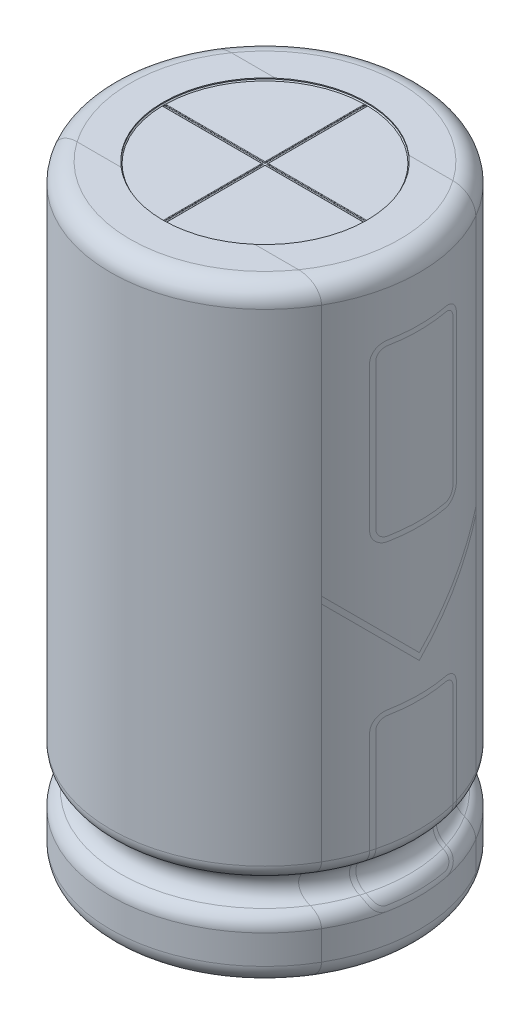
SolidWorks part; units mm, degrees
ref_plane "Front Plane" through (0, 0, 0) normal (0, 0, 1) x (1, 0, 0)
ref_plane "Top Plane" through (0, 0, 0) normal (0, 1, 0) x (1, 0, 0)
ref_plane "Right Plane" through (0, 0, 0) normal (1, 0, 0) x (0, 0, -1)
sketch "Body_Plano" plane through (0, 0, 0) normal (0, 1, 0) x (1, 0, 0)
  circle A0 centre (0, 0) radius 8
  dimension "Diametro" = 16
extrude "Body" add sketch "Body_Plano" along normal blind 31.5
sketch "Cintura_Plano" plane through (0, 0, 0) normal (0, 0, 1) x (1, 0, 0)
  line L0 (8, 31.5) -> (-8, 31.5) construction
  line L1 (0, 0) -> (0, 31.5) construction
  line L2 (-4, 0) -> (-4, 4) construction
  line L3 (-8, 31.5) -> (-8, 0) construction
  line L4 (-6, 4) -> (-7.8125, 4) construction
  line L5 (-4, 4) -> (0, 4) construction
  line L6 (-8, 0) -> (8, 0) construction
  line L7 (-8, 2.5) -> (-8, 5.5)
  line L8 (-6, 3) -> (-7, 3) construction
  line L9 (-4, 2) -> (-8, 2) construction
  line L10 (-6, 2) -> (-6, 4) construction
  line L11 (-7, 3) -> (-7, 2) construction
  line L12 (-7, 2.5) -> (-8, 2.5) construction
  line L13 (-7.5, 2.5) -> (-7.5, 4) construction
  arc A0 (-7.5, 3.25) -> (-7.5, 4.75) centre (-7.8125, 4) ccw
  arc A1 (-7.5, 3.25) -> (-8, 2.5) centre (-7.1875, 2.5) ccw
  arc A2 (-7.5, 4.75) -> (-8, 5.5) centre (-7.1875, 5.5) cw
revolve "Cintura" cut sketch "Cintura_Plano" angle 360 about L1
fillet "F1" radius 1 1 edges at (0, 31.5, 8)
fillet "F2" radius 1 1 edges at (0, 0, 8)
sketch "HS Croquis" plane through (0, 31.5, 0) normal (0, 1, 0) x (1, 0, 0)
  line L0 (0, 0) -> (0, 8) construction
  line L1 (0, 4) -> (6.9282, 4) construction
  circle A0 centre (0, 0) radius 5.2915
  circle A1 centre (0, 0) radius 8 construction
  point P9 (3.4641, 4)
extrude "Hueco Superior" cut sketch "HS Croquis" against normal blind 0.1
sketch "HI Croquis" plane through (0, 0, 0) normal (0, -1, 0) x (1, 0, 0)
  circle A0 centre (0, 0) radius 6.5
  circle A1 centre (0, 0) radius 7 construction
  point P5 (0, 7)
  point P6 (0, 6.5)
  dimension "D1" = 0.5
extrude "Hueco Inferior" cut sketch "HI Croquis" against normal blind 0.1
chamfer "Chaflan Huecos" distance 0.05 angle 45 2 edges at (0, 0.1, -6.5) (0, 31.4, 5.2915)
ref_plane "Plane1" through (8, 0, 0) normal (1, 0, 0) x (0, 0, -1)
sketch "Croquis2" plane through (0, 0.1, 0) normal (0, -1, 0) x (-1, 0, 0)
  line L0 (0, -1.1307) -> (0, 0.9067) construction
  circle A0 centre (-3.75, 0) radius 0.4
  circle A1 centre (3.75, 0) radius 0.4
  dimension "Diametro" = 0.8
  dimension "Pitch" = 7.5
sketch "Croquis3" plane through (0, 31.4, 0) normal (0, 1, 0) x (1, 0, 0)
  line L1 (0, 0.6856) -> (0, -0.5793) construction
  line L2 (-0.0625, 5.2411) -> (-0.0625, 0.0625)
  line L3 (0.829, 0) -> (-0.4995, 0) construction
  line L4 (-0.0625, 0.0625) -> (-5.2411, 0.0625)
  line L7 (0.0625, 0.0625) -> (5.2411, 0.0625)
  line L8 (0.0625, 5.2411) -> (0.0625, 0.0625)
  line L9 (0.0625, -5.2411) -> (0.0625, -0.0625)
  line L10 (0.0625, -0.0625) -> (5.2411, -0.0625)
  line L11 (-0.0625, -0.0625) -> (-5.2411, -0.0625)
  line L12 (-0.0625, -5.2411) -> (-0.0625, -0.0625)
  arc A0 (0.0625, 5.2411) -> (-0.0625, 5.2411) centre (0, 0) ccw
  arc A1 (5.2411, -0.0625) -> (5.2411, 0.0625) centre (0, 0) ccw
  arc A2 (-5.2411, 0.0625) -> (-5.2411, -0.0625) centre (0, 0) ccw
  circle A3 centre (0, 0) radius 5.2415 construction
  arc A4 (-0.0625, -5.2411) -> (0.0625, -5.2411) centre (0, 0) ccw
  dimension "D1" = 0.125
extrude "Cortar-Extruir1" cut sketch "Croquis3" against normal blind 0.05
fillet "Redondeo3" radius 0.025 20 edges at (2.6518, 31.35, 0.0625) (0.0625, 31.35, 2.6518) (0, 31.35, 5.2415) (-0.0625, 31.35, 2.6518) (-2.6518, 31.35, 0.0625) (-5.2415, 31.35, 0) (-2.6518, 31.35, -0.0625) (-0.0625, 31.35, -2.6518) (0, 31.35, -5.2415) (0.0625, 31.35, -2.6518) (2.6518, 31.35, -0.0625) (5.2415, 31.35, 0) (0.0625, 31.4, 2.6518) (2.6518, 31.4, 0.0625) (2.6518, 31.4, -0.0625) (0.0625, 31.4, -2.6518) (-2.6518, 31.4, -0.0625) (-0.0625, 31.4, -2.6518) (-2.6518, 31.4, 0.0625) (-0.0625, 31.4, 2.6518)
sketch "Sketch6" plane through (0, 0, 0) normal (1, 0, 0) x (0, 0, -1)
  line L0 (0, 31.5) -> (0, 0) construction
  line L1 (-4, 31.5) -> (4, 31.5)
  line L2 (4, 23.625) -> (0, 23.625) construction
  line L3 (-4, 0) -> (4, 0)
  line L4 (0, 15.75) -> (8, 15.75) construction
  line L5 (-1.5, 27.9) -> (1.5, 27.9)
  line L6 (-2, 27.4) -> (-2, 19.85)
  line L7 (-1.5, 19.35) -> (1.5, 19.35)
  line L8 (2, 27.4) -> (2, 19.85)
  line L9 (4, 15.75) -> (4, 31.5) construction
  line L10 (8, 5.5) -> (8, 30.5) construction
  line L11 (8, 2.5) -> (-8, 2.5) construction
  line L12 (-3.2906, 15.325) -> (3.6227, 15.325) construction
  line L13 (-1.5, 2.5) -> (1.5, 2.5)
  line L14 (1.5, 15.325) -> (1.5, 11.55) construction
  line L15 (-2.25, 3.25) -> (-2.25, 10.8)
  line L16 (-1.5, 11.55) -> (1.5, 11.55)
  line L17 (2.25, 3.25) -> (2.25, 10.8)
  line L18 (2, 3.25) -> (2, 10.8)
  line L19 (-1.5, 11.3) -> (1.5, 11.3)
  line L20 (-2, 3.25) -> (-2, 10.8)
  line L21 (-1.5, 2.75) -> (1.5, 2.75)
  line L22 (-1.5, 11.55) -> (-1.5, 19.1) construction
  line L23 (0, 13.0839) -> (-4, 17.0839)
  line L24 (4, 31.5) -> (4, 0)
  line L25 (2.25, 27.4) -> (2.25, 19.85)
  line L26 (-1.5, 19.1) -> (1.5, 19.1)
  line L27 (-2.25, 27.4) -> (-2.25, 19.85)
  line L28 (-1.5, 28.15) -> (1.5, 28.15)
  line L29 (-7, 0) -> (7, 0) construction
  line L30 (0, 13.0839) -> (4, 17.0839)
  line L31 (0, 13.4375) -> (-4, 17.4375)
  line L32 (0, 13.4375) -> (4, 17.4375)
  line L33 (5.2915, 31.5) -> (-5.2915, 31.5) construction
  line L34 (1.5, 13.4375) -> (0, 13.4375) construction
  line L36 (-4, 31.5) -> (-4, 0)
  arc A0 (-2, 19.85) -> (-1.5, 19.35) centre (-1.5, 19.85) ccw
  arc A1 (1.5, 19.35) -> (2, 19.85) centre (1.5, 19.85) ccw
  arc A2 (1.5, 27.9) -> (2, 27.4) centre (1.5, 27.4) cw
  arc A3 (-1.5, 27.9) -> (-2, 27.4) centre (-1.5, 27.4) ccw
  arc A4 (1.5, 2.5) -> (2.25, 3.25) centre (1.5, 3.25) ccw
  arc A5 (-1.5, 2.5) -> (-2.25, 3.25) centre (-1.5, 3.25) cw
  arc A6 (-2.25, 10.8) -> (-1.5, 11.55) centre (-1.5, 10.8) cw
  arc A7 (1.5, 11.55) -> (2.25, 10.8) centre (1.5, 10.8) cw
  arc A8 (-1.5, 2.75) -> (-2, 3.25) centre (-1.5, 3.25) cw
  arc A9 (1.5, 2.75) -> (2, 3.25) centre (1.5, 3.25) ccw
  arc A10 (1.5, 11.3) -> (2, 10.8) centre (1.5, 10.8) cw
  arc A11 (-2, 10.8) -> (-1.5, 11.3) centre (-1.5, 10.8) cw
  arc A12 (1.5, 19.1) -> (2.25, 19.85) centre (1.5, 19.85) ccw
  arc A13 (-2.25, 19.85) -> (-1.5, 19.1) centre (-1.5, 19.85) ccw
  arc A14 (-1.5, 28.15) -> (-2.25, 27.4) centre (-1.5, 27.4) ccw
  arc A15 (1.5, 28.15) -> (2.25, 27.4) centre (1.5, 27.4) cw
  point P3 (2, 23.625)
  point P4 (0, 0)
  point P10 (1.5, 15.325)
  point P22 (0, 19.35)
  dimension "D3" = 0.25
  dimension "D4" = 90
  dimension "D2" = 0.5
  dimension "D1" = 0.25
split line "Línea de partición1"
extrude "Saliente-Extruir1" add sketch "Croquis2" along normal offset from surface (1.9 mm away) 1.8 up to face at (0, 0, -5.375) offset beyond the face yes
fillet "Redondeo1" radius 0.2 2 edges at (-3.75, -1.8, 0.4) (3.75, -1.8, 0.4)
